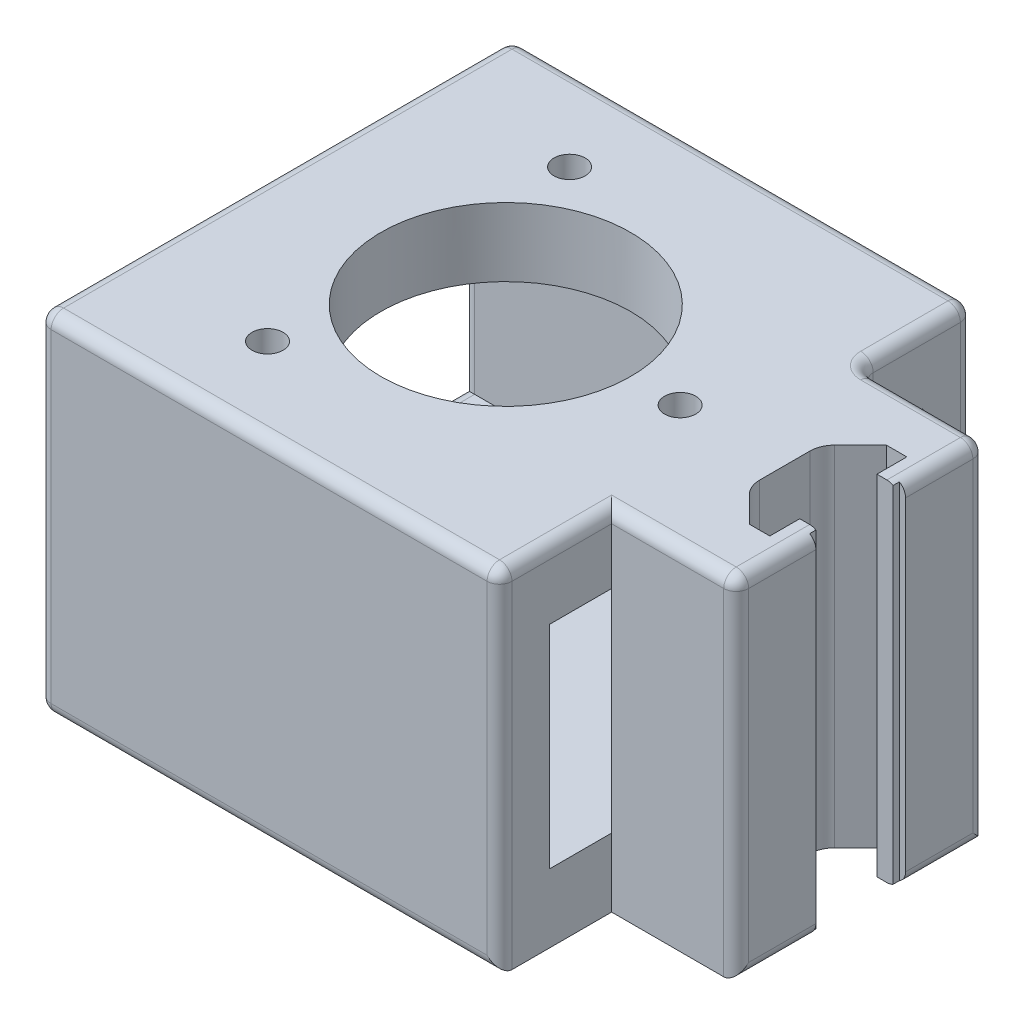
SolidWorks part; units mm, degrees
ref_plane "Front Plane" through (0, 0, 0) normal (0, 0, 1) x (1, 0, 0)
ref_plane "Top Plane" through (0, 0, 0) normal (0, 1, 0) x (1, 0, 0)
ref_plane "Right Plane" through (0, 0, 0) normal (1, 0, 0) x (0, 0, -1)
sketch "Sketch2" plane through (0, 0, 0) normal (1, 0, 0) x (0, 0, -1)
  line L0 (0, -8.5) -> (0, -24.413) construction
  line L1 (19, -14) -> (4, -14)
  line L2 (19, -14) -> (19, 14)
  line L3 (19, 14) -> (-19, 14)
  line L4 (-19, -14) -> (-19, 14)
  line L5 (19, -14) -> (-19, 14) construction
  line L6 (19, 14) -> (-19, -14) construction
  line L7 (-15, -8.5) -> (15, -8.5)
  line L8 (-15, -8.5) -> (-15, 8.5)
  line L9 (-15, 8.5) -> (15, 8.5)
  line L10 (15, -8.5) -> (15, 8.5)
  line L11 (-15, -8.5) -> (15, 8.5) construction
  line L12 (-15, 8.5) -> (15, -8.5) construction
  line L13 (0, -18) -> (-4, -14)
  line L14 (0, -18) -> (4, -14)
  line L15 (-4, -14) -> (-19, -14)
  point P0 (0, 0)
  point P5 (0, 0)
  dimension "D1" = 28
  dimension "D2" = 38
  dimension "D3" = 17
  dimension "D4" = 30
  dimension "D5" = 5.6569
  dimension "D6" = 45
extrude "Boss-Extrude1" add sketch "Sketch2" along normal blind 37
sketch "Sketch3" [suppressed] plane through (0, 14, 0) normal (0, 1, 0) x (1, 0, 0)
  line L0 (37, 19) -> (0, 19) construction
  line L1 (0, 0) -> (37, 0) construction
  line L2 (0, 19) -> (0, -19) construction
  line L3 (37, -19) -> (0, -19) construction
  line L4 (18.5, 19) -> (18.5, -19) construction
  line L5 (37, 19) -> (37, -19) construction
  circle A12 centre (11.5, 0) radius 6
  point P16 (18.5, 0)
  dimension "D1" = 7
  dimension "D5" = 12
extrude "Cut-Extrude1" [suppressed] cut sketch "Sketch3" against normal up to surface (5.5 mm away) contours A12 up to face at (18.5, 8.5, 0)
sketch "Sketch7" plane through (0, 14, 0) normal (0, 1, 0) x (1, 0, 0)
  line L0 (18.5, 19) -> (18.5, -19) construction
  line L1 (37, 19) -> (0, 19) construction
  line L2 (37, -19) -> (0, -19) construction
  circle A0 centre (18.5, 0) radius 10.025
  dimension "D1" = 20.05
extrude "Cut-Extrude4" cut sketch "Sketch7" against normal up to next
hole_wizard "M3x0.5 Tapped Hole1" positions "Sketch10" profile "Sketch9" tap size "M3x0.5" standard "ANSI Metric" end condition up to next
sketch "Sketch10" plane through (0, 14, 0) normal (0, 1, 0) x (1, 0, 0)
  line L0 (18.5, 19) -> (18.5, -19) construction
  line L1 (37, 19) -> (0, 19) construction
  line L2 (37, -19) -> (0, -19) construction
  line L3 (18.5, 0) -> (8.6233, 17.1069) construction
  circle A0 centre (18.5, 0) radius 14 construction
  point P12 (11.5, 12.1244)
  point P20 (32.5, 0)
  point P21 (11.5, -12.1244)
  dimension "D1" = 28
  dimension "D3" = 30
  dimension "D2" = 3
sketch "Sketch9" plane through (11.5, 14, 12.1244) normal (1, 0, 0) x (0, 0, 1)
  line L0 (0, 0) -> (0, 5.5)
  line L1 (0, 5.5) -> (1.25, 5.5)
  line L2 (1.25, 5.5) -> (1.25, 0)
  line L5 (1.25, 0) -> (0, 0)
  line L11 (0, -6.35) -> (0, 107.95) construction
  dimension "Thru Tap Drill Dia." = 2.5
  dimension "Thru Tap Drill Depth" = 5.5
cosmetic thread "Hole Thread1" parameters "D2"=3
cosmetic thread "Hole Thread2" parameters "D2"=3
cosmetic thread "Hole Thread3" parameters "D2"=3
sketch "Sketch4" [suppressed] plane through (0, 14, 0) normal (0, 1, 0) x (1, 0, 0)
  line L0 (0, 0) -> (37, 0) construction
  line L1 (37, 19) -> (37, -19) construction
  line L2 (18.5, 0) -> (1.119, 10.0349) construction
  circle A0 centre (18.5, 0) radius 15 construction
  circle A1 centre (5.5096, 7.5) radius 1.5
  circle A2 centre (18.5, 15) radius 1.5 [skipped]
  circle A3 centre (31.4904, 7.5) radius 1.5
  circle A4 centre (31.4904, -7.5) radius 1.5
  circle A5 centre (18.5, -15) radius 1.5 [skipped]
  circle A6 centre (5.5096, -7.5) radius 1.5
  dimension "D1" = 30
  dimension "D3" = 3
  dimension "D2" = 30
extrude "Cut-Extrude3" [suppressed] cut sketch "Sketch4" against normal up to next
sketch "Sketch6" plane through (0, -14, 0) normal (0, 1, 0) x (1, 0, 0)
  line L0 (37, 0) -> (55.0083, 0) construction
  line L1 (37, 19) -> (37, -19) construction
  line L2 (47, 19.1205) -> (47, -19.1205) construction
  line L3 (47, 3.6) -> (46.5, 3.6)
  line L4 (46.5, 3.6) -> (46.5, 3.1)
  line L5 (46.5, 3.1) -> (45.2, 3.1)
  line L6 (45.2, 3.1) -> (45.2, 5.5)
  line L7 (45.2, 5.5) -> (43.5607, 5.5)
  line L8 (37, 0) -> (50.5625, 13.5625) construction
  line L9 (41.4858, 3.4251) -> (43.5607, 5.5)
  line L10 (40.9, -2.0109) -> (40.9, 2.0109)
  line L11 (41.4858, -3.4251) -> (43.5607, -5.5)
  line L12 (45.2, -5.5) -> (43.5607, -5.5)
  line L13 (45.2, -3.1) -> (45.2, -5.5)
  line L14 (46.5, -3.1) -> (45.2, -3.1)
  line L15 (46.5, -3.6) -> (46.5, -3.1)
  line L16 (47, -3.6) -> (46.5, -3.6)
  line L17 (47, 10) -> (37, 10)
  line L18 (37, 10) -> (37, -10)
  line L19 (37, -10) -> (47, -10)
  line L20 (47, -10) -> (47, -3.6)
  line L21 (47, 10) -> (47, 3.6)
  arc A0 (40.9, 2.0109) -> (41.4858, 3.4251) centre (42.9, 2.0109) cw
  arc A1 (40.9, -2.0109) -> (41.4858, -3.4251) centre (42.9, -2.0109) ccw
  point P27 (40.9, 0)
  line M60 (37, 19) -> (37, 4)
  dimension "D9" = 2
  dimension "D1" = 10
  dimension "D2" = 0.5
  dimension "D3" = 1.8
  dimension "D4" = 7.2
  dimension "D5" = 6.2
  dimension "D6" = 11
  dimension "D7" = 45
  dimension "D8" = 1.5
  dimension "D10" = 3.9
  dimension "D11" = 20
extrude "Boss-Extrude2" add sketch "Sketch6" along normal up to surface (28 mm away) contours L6 L16 L15 L14 L13 | L10 A1 L11 L12 L13 L14 L15 L16 L20 L19 L18 L17 L21 L3 L4 L5 L6 L7 L9 A0 M60 region at (46.75, -14, -3.8236) up to face at (32.5, 14, 1.25)
fillet "Fillet1" radius 1 28 edges at (42, 14, -10) (0, -8.5, 0) (0, 0, 15) (0, 8.5, 0) (0, 0, -15) (0, -14, 11.5) (0, -16, 2) (0, -16, -2) (0, -14, -11.5) (0, 14, 0) (18.5, -14, -19) (37, 0, -19) (18.5, 14, -19) (0, 0, -19) (18.5, 14, 19) (37, 0, 19) (18.5, -14, 19) (0, 0, 19) (37, 14, -14.5) (37, 11.25, -10) (42, 14, 10) (37, 14, 14.5) (47, 0, -10) (47, 0, 10) (47, -14, 6.8) (47, -14, -6.8) (47, 14, 6.8) (47, 14, -6.8)
